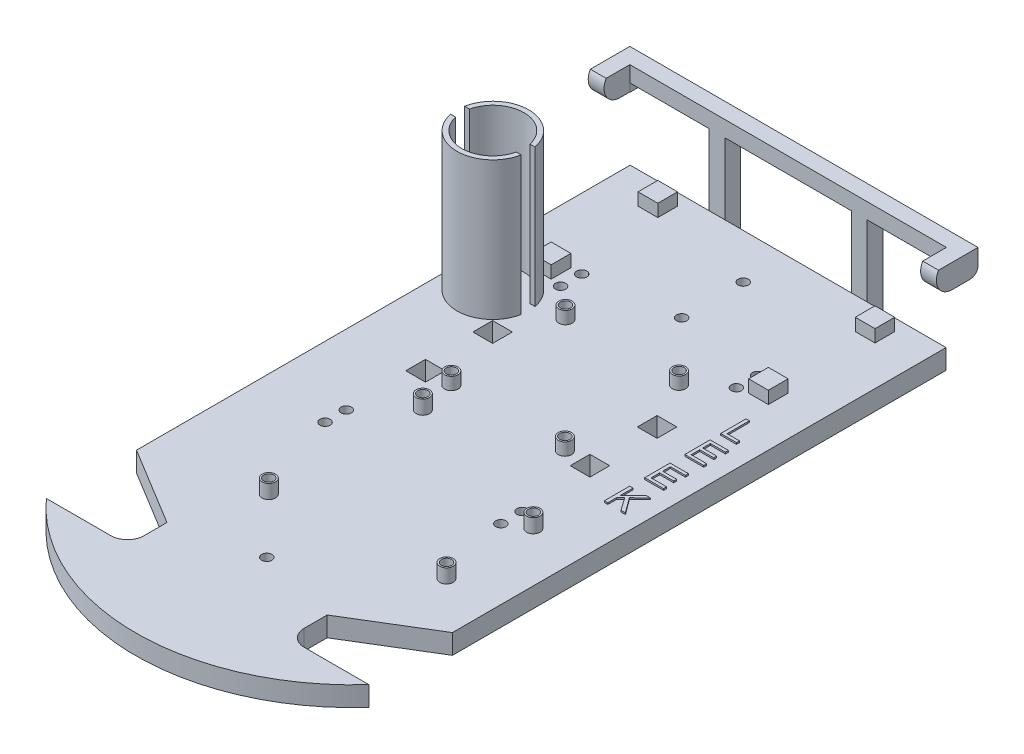
SolidWorks part; units mm, degrees
ref_plane "Front Plane" through (0, 0, 0) normal (0, 0, 1) x (1, 0, 0)
ref_plane "Top Plane" through (0, 0, 0) normal (0, 1, 0) x (1, 0, 0)
ref_plane "Right Plane" through (0, 0, 0) normal (1, 0, 0) x (0, 0, -1)
sketch "Sketch2" plane through (0, 0, 0) normal (0, 1, 0) x (1, 0, 0)
  line L0 (0, 0) -> (101.6, 0)
  line L1 (101.6, 0) -> (101.6, -158.75)
  line L2 (0, 0) -> (0, -158.75)
  line L3 (0, -158.75) -> (25.0357, -173.99)
  line L4 (25.0357, -173.99) -> (25.0357, -181.3822)
  line L5 (50.8, 0) -> (50.8, -228.1413) construction
  line L6 (102.6439, -186.69) -> (81.8722, -186.69)
  line L7 (76.5643, -173.99) -> (76.5643, -181.3822)
  line L8 (-1.0439, -186.69) -> (19.7278, -186.69)
  line L9 (101.6, -158.75) -> (76.5643, -173.99)
  arc A0 (25.0357, -181.3822) -> (19.7278, -186.69) centre (19.7278, -181.3822) cw
  arc A1 (76.5643, -181.3822) -> (81.8722, -186.69) centre (81.8722, -181.3822) ccw
  arc A2 (102.6439, -186.69) -> (-1.0439, -186.69) centre (50.8, -140.0269) cw
  dimension "D4" = 15.24
  dimension "D6" = 69.7512
  dimension "D7" = 12.7
  dimension "D5" = 5.3078
  dimension "D1" = 101.6
  dimension "D2" = 158.75
  dimension "D3" = 29.3094
  dimension "D8" = 103.6879
extrude "Boss-Extrude1" add sketch "Sketch2" against normal blind 6.35
sketch "Sketch3" plane through (0, 0, 0) normal (0, 0, -1) x (-1, 0, 0)
  line L0 (-76.2, -6.35) -> (-76.2, 22.86)
  line L1 (-101.6, -6.35) -> (0, -6.35) construction
  line L2 (-76.2, 22.86) -> (-71.12, 22.86)
  line L3 (-71.12, 22.86) -> (-71.12, -6.35)
  line L4 (-71.12, -6.35) -> (-76.2, -6.35)
  line L5 (-50.8, -6.35) -> (-50.8, 32.5128) construction
  line L6 (-101.6, -6.35) -> (-101.6, 0) construction
  line L7 (-30.48, -6.35) -> (-25.4, -6.35)
  line L8 (-25.4, -6.35) -> (-25.4, 22.86)
  line L9 (-30.48, 22.86) -> (-30.48, -6.35)
  line L10 (-25.4, 22.86) -> (-30.48, 22.86)
  line L11 (-101.6, 22.86) -> (0, 22.86)
  line L12 (0, 22.86) -> (0, 20.32)
  line L13 (0, 20.32) -> (5.183, 20.32)
  line L14 (5.183, 20.32) -> (5.183, 27.94)
  line L19 (5.183, 27.94) -> (-106.783, 27.94)
  line L20 (-101.6, 22.86) -> (-101.6, 20.32)
  line L21 (-101.6, 20.32) -> (-106.783, 20.32)
  line L22 (-106.783, 20.32) -> (-106.783, 27.94)
  point P16 (0, 21.59)
  point P22 (-101.6, 21.59)
  point P26 (-50.8, 27.94)
  dimension "D1" = 5.08
  dimension "D2" = 29.21
  dimension "D3" = 25.4
  dimension "D4" = 5.183
  dimension "D5" = 7.62
  dimension "D6" = 5.08
extrude "Boss-Extrude2" add sketch "Sketch3" along normal blind 5.08 contours L5 L11 L10 L12 L13 L14 L19 | L11 L5 L19 L22 L21 L20 L2 | L8 L10 L9 L7 | L0 L2 L3 L4 region at (79.9153, 25.2314, 0) region at (21.6847, 25.2314, 0)
sketch "Sketch5" plane through (106.783, 0, 0) normal (1, 0, 0) x (0, 0, -1)
  line L0 (5.08, 20.32) -> (5.08, 27.94)
  line L1 (5.08, 20.32) -> (5.08, 27.94) construction
  line L2 (5.08, -6.35) -> (5.08, 22.86) construction
  line L3 (5.08, 27.94) -> (-7.62, 27.94)
  line L5 (-3.2206, 20.32) -> (5.08, 20.32)
  line L6 (5.08, 27.94) -> (0, 27.94) construction
  arc A0 (-7.62, 27.94) -> (-3.2206, 20.32) centre (-3.2206, 25.4) ccw
  dimension "D1" = 5.08
  dimension "D2" = 12.7
extrude "Boss-Extrude3" add sketch "Sketch5" against normal blind 5.08
sketch "Sketch6" plane through (-5.183, 0, 0) normal (-1, 0, 0) x (0, 0, 1)
  line L0 (-5.08, 27.94) -> (-5.08, 20.32)
  line L1 (-5.08, 20.32) -> (3.2206, 20.32)
  line L3 (7.62, 27.94) -> (-5.08, 27.94)
  arc A0 (3.2206, 20.32) -> (7.62, 27.94) centre (3.2206, 25.4) ccw construction
  arc A1 (3.2206, 20.32) -> (7.62, 27.94) centre (3.2206, 25.4) ccw
  dimension "D1" = 5.08
extrude "Boss-Extrude4" add sketch "Sketch6" against normal blind 5.08
fillet "Fillet1" radius 2.54 2 edges at (104.1915, 20.32, -5.08) (-2.5915, 20.32, -5.08)
sketch "Sketch7" plane through (0, 0, 0) normal (0, 1, 0) x (1, 0, 0)
  line L0 (88.9, 0) -> (89.0822, -166.37) construction
  line L1 (101.6, 0) -> (76.2, 0) construction
  line L2 (76.5643, -173.99) -> (101.6, -158.75) construction
  text T0 "<r90>LEEK\r\n</r>" font "Arial" height in points 32
extrude "Boss-Extrude5" add sketch "Sketch7" along normal blind 0.508
ref_plane "Plane2" through (50.8, 0, 0) normal (-1, 0, 0) x (0, 0, 1)
sketch "Sketch8" plane through (0, 0, 0) normal (0, 1, 0) x (1, 0, 0)
  line L0 (101.6, 0) -> (76.2, 0) construction
  line L1 (101.6, -158.75) -> (101.6, 0) construction
  line L2 (101.6, -79.375) -> (0, -79.375) construction
  line L3 (0, 0) -> (0, -158.75) construction
  line L4 (50.8, 0) -> (50.8, -209.7782) construction
  line L5 (71.12, 0) -> (30.48, 0) construction
  circle A0 centre (79.0702, -38.1) radius 1.651
  circle A1 centre (79.0702, -44.9072) radius 1.651
  circle A2 centre (79.0702, -113.8428) radius 1.651
  circle A3 centre (79.0702, -120.65) radius 1.651
  arc A4 (-1.0439, -186.69) -> (102.6439, -186.69) centre (50.8, -140.0269) ccw construction
  circle A5 centre (22.5298, -44.9072) radius 1.651
  circle A6 centre (22.5298, -38.1) radius 1.651
  circle A7 centre (22.5298, -113.8428) radius 1.651
  circle A8 centre (22.5298, -120.65) radius 1.651
  dimension "D1" = 38.1
  dimension "D3" = 3.302
  dimension "D2" = 22.5298
  dimension "D4" = 6.8072
extrude "Cut-Extrude1" cut sketch "Sketch8" against normal through all
sketch "Sketch9" plane through (0, 0, 0) normal (0, 1, 0) x (1, 0, 0)
  line L1 (101.6, -158.75) -> (101.6, 0) construction
  line L5 (0, -79.375) -> (101.6, -79.375) construction
  line L6 (0, 0) -> (0, -158.75) construction
  line L11 (50.8, 5.08) -> (50.8, -209.7782) construction
  line L12 (-5.183, 5.08) -> (106.783, 5.08) construction
  line L21 (27.5329, -65.405) -> (27.5329, -71.755)
  line L22 (74.0671, -65.405) -> (80.4171, -65.405)
  line L23 (74.0671, -65.405) -> (74.0671, -71.755)
  line L24 (74.0671, -71.755) -> (80.4171, -71.755)
  line L25 (80.4171, -65.405) -> (80.4171, -71.755)
  line L26 (27.5329, -71.755) -> (21.1829, -71.755)
  line L27 (21.1829, -65.405) -> (21.1829, -71.755)
  line L28 (27.5329, -65.405) -> (21.1829, -65.405)
  line L29 (27.5329, -93.345) -> (21.1829, -93.345)
  line L30 (21.1829, -93.345) -> (21.1829, -86.995)
  line L31 (27.5329, -86.995) -> (21.1829, -86.995)
  line L32 (27.5329, -93.345) -> (27.5329, -86.995)
  line L33 (74.0671, -86.995) -> (80.4171, -86.995)
  line L34 (80.4171, -93.345) -> (80.4171, -86.995)
  line L35 (74.0671, -93.345) -> (80.4171, -93.345)
  line L36 (74.0671, -93.345) -> (74.0671, -86.995)
  arc A0 (-1.0439, -186.69) -> (102.6439, -186.69) centre (50.8, -140.0269) ccw construction
  dimension "D5" = 21.1829
  dimension "D6" = 6.35
  dimension "D7" = 7.62
extrude "Cut-Extrude3" cut sketch "Sketch9" against normal through all
sketch "Sketch10" plane through (0, 0, 0) normal (0, 1, 0) x (1, 0, 0)
  line L0 (0, -53.34) -> (101.6, -53.34) construction
  line L1 (0, 0) -> (0, -158.75) construction
  line L2 (101.6, -158.75) -> (101.6, 0) construction
  line L4 (50.8, 5.08) -> (50.8, -209.7782) construction
  line L5 (-5.183, 5.08) -> (106.783, 5.08) construction
  line L6 (76.2, 0) -> (71.12, 0) construction
  circle A0 centre (69.0562, -53.34) radius 1.651
  circle A1 centre (69.0562, -90.043) radius 1.651
  arc A2 (-1.0439, -186.69) -> (102.6439, -186.69) centre (50.8, -140.0269) ccw construction
  circle A3 centre (32.5437, -53.34) radius 1.651
  circle A4 centre (32.5437, -90.043) radius 1.651
  circle A5 centre (69.0562, -53.34) radius 2.159
  circle A6 centre (69.0562, -90.043) radius 2.159
  circle A7 centre (32.5437, -53.34) radius 2.159
  circle A8 centre (32.5437, -90.043) radius 2.159
  dimension "D1" = 3.302
  dimension "D4" = 36.703
  dimension "D5" = 4.318
  dimension "D2" = 53.34
  dimension "D3" = 18.2562
extrude "Cut-Extrude4" cut sketch "Sketch10" against normal through all contours A4 | A1 | A0 | A3 region at (69.0562, 0, 53.34) region at (69.0562, 0, 90.043) region at (32.5437, 0, 53.34) region at (32.5437, 0, 90.043)
sketch "Sketch11" plane through (0, 0, 0) normal (0, 1, 0) x (1, 0, 0)
  text T0 "SPEED" font "Arial" height in points 32
extrude "Boss-Extrude6" [suppressed] add sketch "Sketch11" along normal blind 0.508
sketch "Sketch12" plane through (0, 0, 0) normal (0, 1, 0) x (1, 0, 0)
  line L0 (101.6, -158.75) -> (101.6, 0) construction
  circle A0 centre (85.598, -116.713) radius 1.651
  circle A1 centre (34.798, -101.473) radius 1.651
  circle A2 centre (33.528, -149.7341) radius 1.651
  circle A3 centre (32.5437, -90.043) radius 1.651 construction
  circle A4 centre (85.598, -144.653) radius 1.651
  circle A5 centre (34.798, -101.473) radius 2.159
  circle A6 centre (85.598, -116.713) radius 2.159
  circle A7 centre (85.598, -144.653) radius 2.159
  circle A8 centre (33.528, -149.7341) radius 2.159
  dimension "D1" = 16.002
  dimension "D2" = 3.302
  dimension "D3" = 3.302
  dimension "D4" = 48.2778
  dimension "D5" = 11.43
  dimension "D8" = 27.94
  dimension "D10" = 4.318
  dimension "D6" = 50.8
  dimension "D7" = 15.24
  dimension "D9" = 1.27
extrude "Cut-Extrude6" cut sketch "Sketch12" against normal through all contours A2 | A4 | A0 | A1 region at (85.598, 0, 116.713) region at (34.798, 0, 101.473) region at (33.528, 0, 149.7341) region at (85.598, 0, 144.653)
extrude "Boss-Extrude7" add sketch "Sketch10<3>" along normal blind 4
sketch "Sketch10<3>" plane through (0, 0, 0) normal (0, 1, 0) x (1, 0, 0) same geometry as "Sketch10"
extrude "Boss-Extrude8" add sketch "Sketch12<3>" along normal blind 4.5
sketch "Sketch12<3>" plane through (0, 0, 0) normal (0, 1, 0) x (1, 0, 0) same geometry as "Sketch12"
sketch "Sketch18" plane through (0, 0, 0) normal (0, 1, 0) x (1, 0, 0)
  line L0 (-0.103, 0) -> (101.703, 0) construction
  line L1 (12.7, -3.81) -> (88.9, -3.81)
  line L2 (12.7, -3.81) -> (12.7, -44.45)
  line L3 (12.7, -44.45) -> (88.9, -44.45)
  line L4 (88.9, -3.81) -> (88.9, -44.45)
  line L5 (12.7, -3.81) -> (88.9, -44.45) construction
  line L6 (12.7, -44.45) -> (88.9, -3.81) construction
  line L7 (50.8, -209.7782) -> (50.8, 5.08) construction
  line L8 (-5.183, 5.08) -> (106.783, 5.08) construction
  line L9 (12.7, -24.13) -> (88.9, -24.13) construction
  line L10 (12.7, -44.45) -> (19.05, -44.45)
  line L11 (12.7, -44.45) -> (12.7, -38.1)
  line L12 (12.7, -38.1) -> (19.05, -38.1)
  line L13 (19.05, -44.45) -> (19.05, -38.1)
  line L14 (12.7, -10.16) -> (19.05, -10.16)
  line L15 (19.05, -3.81) -> (19.05, -10.16)
  line L16 (12.7, -3.81) -> (19.05, -3.81)
  line L17 (12.7, -3.81) -> (12.7, -10.16)
  line L18 (88.9, -3.81) -> (82.55, -3.81)
  line L19 (82.55, -3.81) -> (82.55, -10.16)
  line L20 (88.9, -10.16) -> (82.55, -10.16)
  line L21 (88.9, -3.81) -> (88.9, -10.16)
  line L22 (88.9, -38.1) -> (82.55, -38.1)
  line L23 (82.55, -44.45) -> (82.55, -38.1)
  line L24 (88.9, -44.45) -> (82.55, -44.45)
  line L25 (88.9, -44.45) -> (88.9, -38.1)
  circle A0 centre (50.7467, -14.384) radius 1.651
  circle A1 centre (50.8, -34.2341) radius 1.651
  arc A2 (-1.0439, -186.69) -> (102.6439, -186.69) centre (50.8, -140.0269) ccw construction
  point P0 (50.8, -24.13)
  dimension "D4" = 38.0467
  dimension "D5" = 3.302
  dimension "D7" = 19.8501
  dimension "D8" = 6.35
  dimension "D9" = 6.35
  dimension "D1" = 40.64
  dimension "D2" = 76.2
  dimension "D3" = 3.81
  dimension "D6" = 10.574
extrude "Boss-Extrude9" add sketch "Sketch18" along normal blind 4 contours L3 L13 L12 L2 | L23 L3 L4 L22 | L17 L14 L15 L16 | L21 L20 L19 L18 region at (15.875, 0, 41.275) region at (85.725, 0, 41.275)
extrude "Cut-Extrude11" cut sketch "Sketch18<3>" against normal through all contours A1 | A0 region at (50.7467, 0, 14.384) region at (50.8, 0, 34.2341)
sketch "Sketch18<3>" plane through (0, 0, 0) normal (0, 1, 0) x (1, 0, 0) same geometry as "Sketch18"
sketch "Sketch16" [suppressed] plane through (0, -5.842, 0) normal (0, 1, 0) x (1, 0, 0)
  line L0 (16.3532, -2.4498) -> (16.3532, -33.1102) construction
  line L1 (20.9785, -19.8793) -> (24.7275, -19.8793)
  line L2 (20.9785, -19.8793) -> (20.9785, -27.8803)
  line L3 (20.9785, -27.8803) -> (24.7275, -27.8803)
  line L4 (24.7275, -19.8793) -> (24.7275, -27.8803)
  line L5 (20.9785, -19.8793) -> (24.7275, -27.8803) construction
  line L6 (20.9785, -27.8803) -> (24.7275, -19.8793) construction
  line L7 (17.6232, -34.3802) -> (83.9768, -34.3802) construction
  point P0 (22.853, -23.8798)
  dimension "D1" = 3.749
  dimension "D2" = 8.001
  dimension "D3" = 4.6253
  dimension "D4" = 6.4999
extrude "Cut-Extrude9" [suppressed] cut sketch "Sketch16" against normal through all
sketch "Sketch17" plane through (0, 0, 0) normal (0, 1, 0) x (1, 0, 0)
  line L0 (50.8, 5.08) -> (50.8, -209.7782) construction
  line L1 (-5.183, 5.08) -> (106.783, 5.08) construction
  arc A0 (-1.0439, -186.69) -> (102.6439, -186.69) centre (50.8, -140.0269) ccw construction
  circle A1 centre (50.8, -167.64) radius 1.651
  dimension "D1" = 3.302
  dimension "D2" = 6.35
extrude "Cut-Extrude10" cut sketch "Sketch17" against normal through all
sketch "Sketch19" plane through (0, 0, 0) normal (0, 1, 0) x (1, 0, 0)
  line L0 (0, 0) -> (0, -158.75) construction
  line L1 (25.4, 0) -> (0, 0) construction
  line L3 (2.9987, -54.6749) -> (9.3487, -54.6749)
  line L5 (2.9987, -59.1171) -> (9.3487, -59.1171)
  line L6 (9.3487, -54.6749) -> (9.3487, -59.1171)
  arc A0 (2.9987, -59.1171) -> (2.9987, -54.6749) centre (12.7437, -56.896) ccw
  circle A1 centre (12.7437, -56.896) radius 11.557
  dimension "D1" = 19.9898
  dimension "D7" = 23.114
  dimension "D2" = 12.7437
  dimension "D3" = 56.896
  dimension "D4" = 6.35
  dimension "D5" = 4.4422
  dimension "D6" = 9.745
extrude "Boss-Extrude11" add sketch "Sketch19" along normal blind 44.45 contours A1 A0 L5 L6 L3 | L5 A0 L3 L6 region at (13.4199, 0, 56.896) region at (1.5136, 0, 56.896)
extrude "Cut-Extrude12" cut sketch "Sketch19<3>" along normal up to surface (44.45 mm away) contours A0 L3 L6 L5 up to face at (12.7437, 44.45, 68.453)
sketch "Sketch19<3>" plane through (0, 0, 0) normal (0, 1, 0) x (1, 0, 0) same geometry as "Sketch19"
sketch "Sketch20" plane through (0, 44.45, 0) normal (0, 1, 0) x (1, 0, 0)
  line L0 (9.3487, -54.6749) -> (1.4021, -54.6749)
  line L1 (9.3487, -59.1171) -> (1.4021, -59.1171)
  line L2 (12.7437, -45.339) -> (12.7437, -68.453) construction
  line L3 (9.3487, -54.6749) -> (9.3487, -59.1171)
  line L7 (16.1387, -54.6749) -> (24.0853, -54.6749)
  line L8 (16.1387, -59.1171) -> (24.0853, -59.1171)
  line L9 (16.1387, -54.6749) -> (16.1387, -59.1171)
  circle A0 centre (12.7437, -56.896) radius 11.557 construction
  arc A1 (1.4021, -59.1171) -> (1.4021, -54.6749) centre (12.7437, -56.896) cw
  circle A2 centre (12.7437, -56.896) radius 11.557 construction
  arc A4 (24.0853, -59.1171) -> (24.0853, -54.6749) centre (12.7437, -56.896) ccw
  line M1 (2.9987, -59.1171) -> (9.3487, -59.1171)
  line M2 (9.3487, -59.1171) -> (9.3487, -54.6749)
  line M3 (9.3487, -54.6749) -> (2.9987, -54.6749)
  circle M5 centre (12.7437, -56.896) radius 11.557
extrude "Cut-Extrude13" cut sketch "Sketch20" against normal up to surface (44.45 mm away) and the other way through all contours L1 L0 M1 M2 M3 M5 | L7 A4 L8 L9 region at (5.3032, 44.45, 56.896) up to face at (12.7437, 0, 45.339)
